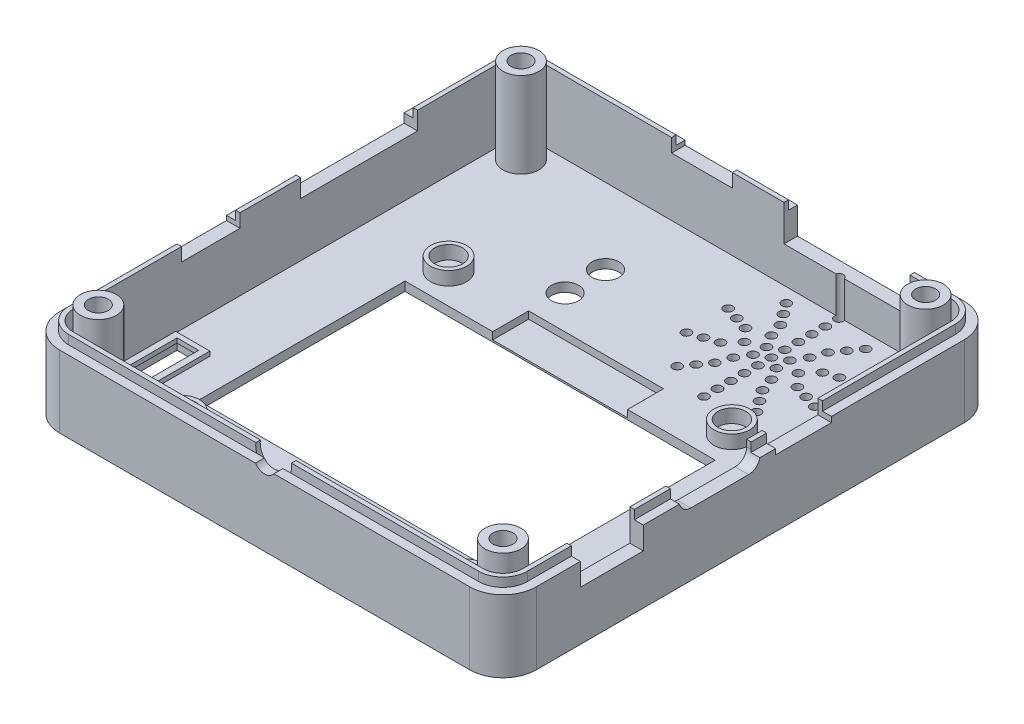
SolidWorks part; units mm, degrees
ref_plane "Front Plane" through (0, 0, 0) normal (0, 0, 1) x (1, 0, 0)
ref_plane "Top Plane" through (0, 0, 0) normal (0, 1, 0) x (1, 0, 0)
ref_plane "Right Plane" through (0, 0, 0) normal (1, 0, 0) x (0, 0, -1)
sketch "Sketch1" plane through (0, 0, 0) normal (0, 1, 0) x (1, 0, 0)
  line L5 (-25.5, 23.8) -> (-25.5, -23.8)
  line L6 (-22.8, 26) -> (22.8, 26)
  line L18 (-25, 23.8) -> (-25, -23.8)
  line L19 (-22.8, -26) -> (22.8, -26)
  line L20 (25, 23.8) -> (25, -23.8)
  line L21 (-25, 26) -> (25, -26) construction
  line L22 (-25, -26) -> (25, 26) construction
  line L23 (-22.8, -26.5) -> (22.8, -26.5)
  line L24 (25.5, 23.8) -> (25.5, -23.8)
  line L25 (-22.8, 26.5) -> (22.8, 26.5)
  line L26 (-26.5, 23.8) -> (-26.5, -23.8)
  line L27 (-22.8, -27.5) -> (22.8, -27.5)
  line L28 (26.5, 23.8) -> (26.5, -23.8)
  line L29 (-22.8, 27.5) -> (22.8, 27.5)
  line L48 (17, 15.5) -> (17, 13.5)
  line L52 (17, -13.5) -> (17, -15.5)
  circle A20 centre (-22.5, 23.5) radius 1.1
  circle A21 centre (22.5, 23.5) radius 1.1
  circle A22 centre (-22.5, -23.5) radius 1.1
  circle A23 centre (22.5, -23.5) radius 1.1
  circle A24 centre (-22.5, 23.5) radius 2
  circle A25 centre (22.5, 23.5) radius 2
  circle A26 centre (22.5, -23.5) radius 2
  circle A27 centre (-22.5, -23.5) radius 2
  arc A28 (-22.8, -26) -> (-25, -23.8) centre (-22.8, -23.8) cw
  arc A29 (25, -23.8) -> (22.8, -26) centre (22.8, -23.8) cw
  arc A30 (25, 23.8) -> (22.8, 26) centre (22.8, 23.8) ccw
  arc A31 (-22.8, 26) -> (-25, 23.8) centre (-22.8, 23.8) ccw
  arc A32 (-22.8, -26.5) -> (-25.5, -23.8) centre (-22.8, -23.8) cw
  arc A33 (25.5, -23.8) -> (22.8, -26.5) centre (22.8, -23.8) cw
  arc A34 (25.5, 23.8) -> (22.8, 26.5) centre (22.8, 23.8) ccw
  arc A35 (-22.8, 26.5) -> (-25.5, 23.8) centre (-22.8, 23.8) ccw
  arc A36 (-22.8, -27.5) -> (-26.5, -23.8) centre (-22.8, -23.8) cw
  arc A37 (26.5, -23.8) -> (22.8, -27.5) centre (22.8, -23.8) cw
  arc A38 (26.5, 23.8) -> (22.8, 27.5) centre (22.8, 23.8) ccw
  arc A39 (-22.8, 27.5) -> (-26.5, 23.8) centre (-22.8, 23.8) ccw
  point P0 (0, 0)
  dimension "D3" = 2.2
  dimension "D6" = 2.2
  dimension "D7" = 2.5
  dimension "D8" = 2.5
  dimension "D9" = 2.5
  dimension "D10" = 2.5
  dimension "D11" = 2.5
  dimension "D12" = 2.5
  dimension "D13" = 2.5
  dimension "D14" = 2.5
  dimension "D15" = 4
  dimension "D16" = 4
  dimension "D17" = 4
  dimension "D18" = 4
  dimension "D19" = 2.2
  dimension "D20" = 0.5
  dimension "D4" = 2.2
  dimension "D5" = 2.2
  dimension "D1" = 52
  dimension "D2" = 50
  dimension "D22" = 53
  dimension "D21" = 1.5
extrude "Boss-Extrude1" add sketch "Sketch1" along normal blind 8 contours L29 A39 L26 A36 L27 A37 L28 A38 A35 L25 A34 L24 A33 L23 A32 L5 region at (-24.8762, 0, -25.8762)
extrude "Boss-Extrude2" add sketch "Sketch1<16>" along normal blind 9 contours L25 A35 L5 A32 L23 A33 L24 A34 A31 L6 A30 L20 A29 L19 A28 L18 region at (-24.6572, 0, -25.6572)
sketch "Sketch1<16>" plane through (0, 0, 0) normal (0, 1, 0) x (1, 0, 0) same geometry as "Sketch1"
extrude "Boss-Extrude3" add sketch "Sketch1<17>" along normal blind 10.5 separate body contours A27 A22 | A24 A20 | A25 A21 | A26 A23 region at (-24.4434, 0, -23.5) region at (20.5566, 0, -23.5) region at (20.5566, 0, 23.5) region at (-24.4434, 0, 23.5)
sketch "Sketch1<17>" plane through (0, 0, 0) normal (0, 1, 0) x (1, 0, 0) same geometry as "Sketch1"
extrude "Boss-Extrude4" add sketch "Sketch1<18>" along normal blind 1 contours L6 A31 L18 A28 L19 A29 L20 A30 A24 A25 A26 A27 | A23 | A22 | A21 | A20 region at (0, 0, 0) region at (-22.5, 0, -23.5) region at (22.5, 0, -23.5) region at (-22.5, 0, 23.5) region at (22.5, 0, 23.5)
sketch "Sketch1<18>" plane through (0, 0, 0) normal (0, 1, 0) x (1, 0, 0) same geometry as "Sketch1"
sketch "Sketch2" plane through (0, 0, -27.5) normal (0, 0, -1) x (-1, 0, 0)
  line L0 (22.8, 9) -> (-22.8, 9) construction
  line L1 (-18.25, 9) -> (-4.25, 9)
  line L2 (-18.25, 9) -> (-18.25, 5)
  line L3 (-18.25, 5) -> (-4.25, 5)
  line L4 (-4.25, 9) -> (-4.25, 5)
  line L5 (-26.5, 8) -> (-26.5, 0) construction
  line L6 (1.5, 9) -> (8.25, 9)
  line L7 (1.5, 9) -> (1.5, 7.5)
  line L8 (1.5, 7.5) -> (8.25, 7.5)
  line L9 (8.25, 9) -> (8.25, 7.5)
  dimension "D1" = 8.25
  dimension "D2" = 14
  dimension "D3" = 5.75
  dimension "D4" = 4
  dimension "D5" = 1.5
  dimension "D6" = 6.75
extrude "Cut-Extrude3" cut sketch "Sketch2" against normal blind 5
sketch "Sketch4" plane through (0, 0, 27.5) normal (0, 0, 1) x (1, 0, 0)
  line L0 (26.5, 8) -> (26.5, 0) construction
  line L1 (-22.8, 8) -> (22.8, 8) construction
  circle A1 centre (0, 8.71) radius 1.25
  dimension "D2" = 26.5
  dimension "D1" = 2.5
  dimension "D3" = 0.71
extrude "Cut-Extrude4" cut sketch "Sketch4" against normal blind 5
sketch "Sketch6" plane through (26.5, 0, 0) normal (1, 0, 0) x (0, 0, -1)
  line L0 (23.8, 9) -> (-23.8, 9) construction
  line L1 (-18.9, 9) -> (-11.9, 9)
  line L2 (-18.9, 9) -> (-18.9, 5.5)
  line L3 (-18.9, 5.5) -> (-11.9, 5.5)
  line L4 (-11.9, 9) -> (-11.9, 5.5)
  line L6 (-7.9, 9) -> (1.1, 9)
  line L7 (-7.9, 9) -> (-7.9, 8.28)
  line L8 (-6.62, 7) -> (-0.18, 7)
  line L9 (1.1, 9) -> (1.1, 8.28)
  line L10 (9.02, 9) -> (2.82, 9)
  line L11 (9.02, 9) -> (9.02, 7.4)
  line L12 (9.02, 7.4) -> (2.82, 7.4)
  line L13 (2.82, 9) -> (2.82, 7.4)
  line L14 (27.5, 8) -> (27.5, 0) construction
  arc A0 (1.1, 8.28) -> (-0.18, 7) centre (-0.18, 8.28) cw
  arc A1 (-6.62, 7) -> (-7.9, 8.28) centre (-6.62, 8.28) cw
  point P18 (1.1, 7)
  point P21 (-7.9, 7)
  dimension "D10" = 1.28
  dimension "D1" = 1.72
  dimension "D2" = 6.2
  dimension "D3" = 4
  dimension "D4" = 1.6
  dimension "D5" = 18.48
  dimension "D6" = 9
  dimension "D7" = 7
  dimension "D8" = 3.5
  dimension "D9" = 2
extrude "Cut-Extrude5" cut sketch "Sketch6" against normal blind 5
sketch "Sketch7" plane through (-26.5, 0, 0) normal (-1, 0, 0) x (0, 0, 1)
  line L0 (-23.8, 9) -> (23.8, 9) construction
  line L1 (-14.5, 9) -> (-1.5, 9)
  line L2 (-14.5, 9) -> (-14.5, 7)
  line L3 (-14.5, 7) -> (-1.5, 7)
  line L4 (-1.5, 9) -> (-1.5, 7)
  line L5 (-27.5, 8) -> (-27.5, 0) construction
  line L7 (5.25, 9) -> (11.75, 9)
  line L8 (5.25, 9) -> (5.25, 7.5)
  line L9 (5.25, 7.5) -> (11.75, 7.5)
  line L10 (11.75, 9) -> (11.75, 7.5)
  dimension "D1" = 2
  dimension "D2" = 13
  dimension "D3" = 13
  dimension "D4" = 6.5
  dimension "D5" = 6.75
  dimension "D6" = 1.5
extrude "Cut-Extrude6" cut sketch "Sketch7" against normal blind 5
sketch "Sketch8" plane through (0, 0, 0) normal (0, -1, 0) x (1, 0, 0)
  line L0 (-22.8, 27.5) -> (22.8, 27.5) construction
  line L1 (-24.25, 21) -> (-21.25, 21)
  line L2 (-24.25, 21) -> (-24.25, 13)
  line L3 (-24.25, 13) -> (-21.25, 13)
  line L4 (-21.25, 21) -> (-21.25, 13)
  line L5 (-26.5, -23.8) -> (-26.5, 23.8) construction
  dimension "D1" = 3
  dimension "D2" = 8
  dimension "D3" = 6.5
  dimension "D4" = 2.25
extrude "Cut-Extrude7" cut sketch "Sketch8" against normal blind 5
sketch "Sketch9" plane through (0, 1, 0) normal (0, 1, 0) x (1, 0, 0)
  line L0 (-22.8, -26) -> (22.8, -26) construction
  line L1 (17.75, -23) -> (-17.75, -23)
  line L2 (17.75, -23) -> (17.75, 10.7)
  line L3 (17.75, 10.7) -> (-17.75, 10.7)
  line L4 (-17.75, -23) -> (-17.75, 10.7)
  line L5 (17.75, -23) -> (-17.75, 10.7) construction
  line L6 (17.75, 10.7) -> (-17.75, -23) construction
  line L7 (25, 23.8) -> (25, -23.8) construction
  line L8 (-25, 23.8) -> (-25, -23.8) construction
  line L10 (-17.25, 5.35) -> (17.25, 5.35)
  line L11 (-17.25, 5.35) -> (-17.25, -17.65)
  line L12 (-17.25, -17.65) -> (17.25, -17.65)
  line L13 (17.25, 5.35) -> (17.25, -17.65)
  line L14 (-17.25, 5.35) -> (17.25, -17.65) construction
  line L15 (-17.25, -17.65) -> (17.25, 5.35) construction
  circle A0 centre (-15.75, 8.7) radius 1.55
  circle A1 centre (15.75, 8.7) radius 1.55
  circle A2 centre (-15.75, -21) radius 1.55
  circle A3 centre (15.75, -21) radius 1.55
  circle A4 centre (-15.75, 8.7) radius 2
  circle A5 centre (15.75, 8.7) radius 2
  circle A6 centre (15.75, -21) radius 2
  circle A7 centre (-15.75, -21) radius 2
  point P0 (0, -6.15)
  point P23 (0, -6.15)
  dimension "D6" = 2
  dimension "D7" = 2
  dimension "D8" = 2
  dimension "D9" = 2
  dimension "D10" = 2
  dimension "D11" = 2
  dimension "D12" = 2
  dimension "D13" = 2
  dimension "D14" = 23
  dimension "D1" = 3
  dimension "D2" = 35.5
  dimension "D3" = 7.25
  dimension "D4" = 7.25
  dimension "D5" = 33.7
  dimension "D15" = 34.5
  dimension "D16" = 0.5
extrude "Boss-Extrude5" add sketch "Sketch9" along normal blind 1.5 contours A5 A1 | A4 A0 | A7 A2 | A6 A3 region at (14.3758, 1, 19.6258) region at (-17.1242, 1, 22.3742) region at (14.3758, 1, -7.3258) region at (-17.1242, 1, -10.0742)
extrude "Cut-Extrude8" cut sketch "Sketch9<3>" against normal blind 10 contours L13 L10 L11 L12 region at (0, 1, 6.15)
sketch "Sketch9<3>" plane through (0, 1, 0) normal (0, 1, 0) x (1, 0, 0) same geometry as "Sketch9"
sketch "Sketch10" plane through (0, 0, 26) normal (0, 0, -1) x (-1, 0, 0)
  line L0 (22.8, 9) -> (1.2159, 9) construction
  circle A0 centre (0, 8.71) radius 2
  dimension "D1" = 0.29
extrude "Cut-Extrude9" cut sketch "Sketch10" against normal blind 0.5
sketch "Sketch12" plane through (0, 0, 0) normal (0, -1, 0) x (1, 0, 0)
  line L0 (-22.8, -27.5) -> (22.8, -27.5) construction
  line L2 (-26.5, -23.8) -> (-26.5, 23.8) construction
  circle A0 centre (-7.2, -17.6) radius 1.5
  circle A1 centre (-7.2, -13.1) radius 1.5
  dimension "D1" = 9.9
  dimension "D2" = 19.3
  dimension "D4" = 4.5
  dimension "D5" = 14.4
  dimension "D6" = 3
  dimension "D3" = 2
extrude "Cut-Extrude11" cut sketch "Sketch12" against normal blind 10
sketch "Sketch13" plane through (0, 0, 0) normal (0, -1, 0) x (1, 0, 0)
  line L0 (26.5, -23.8) -> (26.5, 23.8) construction
  line L1 (-17.25, -5.35) -> (17.25, -5.35) construction
  circle A0 centre (10.5, -18.35) radius 0.5
  circle A2 centre (10.5, -16.85) radius 0.5
  circle A3 centre (10.5, -15.35) radius 0.5
  circle A4 centre (10.5, -13.85) radius 0.5
  circle A5 centre (10.5, -12.35) radius 0.5
  circle A6 centre (10.5, -10.85) radius 0.5
  circle A7 centre (14.9084, -12.2824) radius 0.5
  circle A8 centre (17.6329, -16.0324) radius 0.5
  circle A9 centre (17.6329, -20.6676) radius 0.5
  circle A10 centre (14.9084, -24.4176) radius 0.5
  circle A11 centre (10.5, -25.85) radius 0.5
  circle A12 centre (6.0916, -24.4176) radius 0.5
  circle A13 centre (3.3671, -20.6676) radius 0.5
  circle A14 centre (3.3671, -16.0324) radius 0.5
  circle A15 centre (6.0916, -12.2824) radius 0.5
  circle A16 centre (14.0267, -13.4959) radius 0.5
  circle A17 centre (16.2063, -16.4959) radius 0.5
  circle A18 centre (16.2063, -20.2041) radius 0.5
  circle A19 centre (14.0267, -23.2041) radius 0.5
  circle A20 centre (10.5, -24.35) radius 0.5
  circle A21 centre (6.9733, -23.2041) radius 0.5
  circle A22 centre (4.7937, -20.2041) radius 0.5
  circle A23 centre (4.7937, -16.4959) radius 0.5
  circle A24 centre (6.9733, -13.4959) radius 0.5
  circle A25 centre (13.145, -14.7094) radius 0.5
  circle A26 centre (14.7798, -16.9594) radius 0.5
  circle A27 centre (14.7798, -19.7406) radius 0.5
  circle A28 centre (13.145, -21.9906) radius 0.5
  circle A29 centre (10.5, -22.85) radius 0.5
  circle A30 centre (7.855, -21.9906) radius 0.5
  circle A31 centre (6.2202, -19.7406) radius 0.5
  circle A32 centre (6.2202, -16.9594) radius 0.5
  circle A33 centre (7.855, -14.7094) radius 0.5
  circle A34 centre (12.6213, -16.2287) radius 0.5
  circle A35 centre (13.5, -18.35) radius 0.5
  circle A36 centre (12.6213, -20.4713) radius 0.5
  circle A37 centre (10.5, -21.35) radius 0.5
  circle A38 centre (8.3787, -20.4713) radius 0.5
  circle A39 centre (7.5, -18.35) radius 0.5
  circle A40 centre (8.3787, -16.2287) radius 0.5
  circle A41 centre (11.799, -17.6) radius 0.5
  circle A42 centre (11.799, -19.1) radius 0.5
  circle A43 centre (10.5, -19.85) radius 0.5
  circle A44 centre (9.201, -19.1) radius 0.5
  circle A45 centre (9.201, -17.6) radius 0.5
  point P37 (10.5, -18.35)
  point P57 (10.5, -18.35)
  point P75 (10.5, -18.35)
  point P90 (10.5, -18.35)
  point P102 (10.5, -18.35)
  dimension "D1" = 1
  dimension "D2" = 16
  dimension "D3" = 13
  dimension "D5" = 6
extrude "Cut-Extrude12" cut sketch "Sketch13" against normal blind 10
sketch "Sketch18" plane through (0, 1, 0) normal (0, 1, 0) x (1, 0, 0)
  line L0 (-17.25, 5.35) -> (17.25, 5.35) construction
  line L1 (-7.5, 5.35) -> (7.5, 5.35)
  line L2 (-7.5, 5.35) -> (-7.5, 9.35)
  line L3 (-7.5, 9.35) -> (7.5, 9.35)
  line L4 (7.5, 5.35) -> (7.5, 9.35)
  line L5 (-17.25, 5.35) -> (-17.25, -17.65) construction
  line L6 (17.25, 5.35) -> (17.25, -17.65) construction
  dimension "D1" = 9.75
  dimension "D2" = 15
  dimension "D3" = 9.75
  dimension "D4" = 4
extrude "Cut-Extrude13" cut sketch "Sketch18" against normal blind 0.8
sketch "Sketch21" plane through (0, 1, 0) normal (0, 1, 0) x (1, 0, 0)
  line L0 (-24.25, -13) -> (-24.25, -21) construction
  line L1 (-24.65, -12.75) -> (-20.85, -12.75)
  line L2 (-24.65, -12.75) -> (-24.65, -21.25)
  line L3 (-24.65, -21.25) -> (-20.85, -21.25)
  line L4 (-20.85, -12.75) -> (-20.85, -21.25)
  line L5 (-21.25, -21) -> (-21.25, -13) construction
  line L6 (-24.25, -21) -> (-21.25, -21) construction
  line L7 (-21.25, -13) -> (-24.25, -13) construction
  line L9 (-23.95, -13.3) -> (-21.55, -13.3)
  line L10 (-23.95, -13.3) -> (-23.95, -20.7)
  line L11 (-23.95, -20.7) -> (-21.55, -20.7)
  line L12 (-21.55, -13.3) -> (-21.55, -20.7)
  line L13 (-23.95, -13.3) -> (-21.55, -20.7) construction
  line L14 (-23.95, -20.7) -> (-21.55, -13.3) construction
  point P12 (-22.75, -17)
  dimension "D1" = 0.4
  dimension "D2" = 0.4
  dimension "D3" = 3.8
  dimension "D4" = 8.5
  dimension "D5" = 0.25
  dimension "D6" = 0.25
  dimension "D7" = 0.3
  dimension "D8" = 0.3
  dimension "D9" = 0.3
  dimension "D10" = 0.3
extrude "Boss-Extrude9" add sketch "Sketch21" along normal blind 0.5
